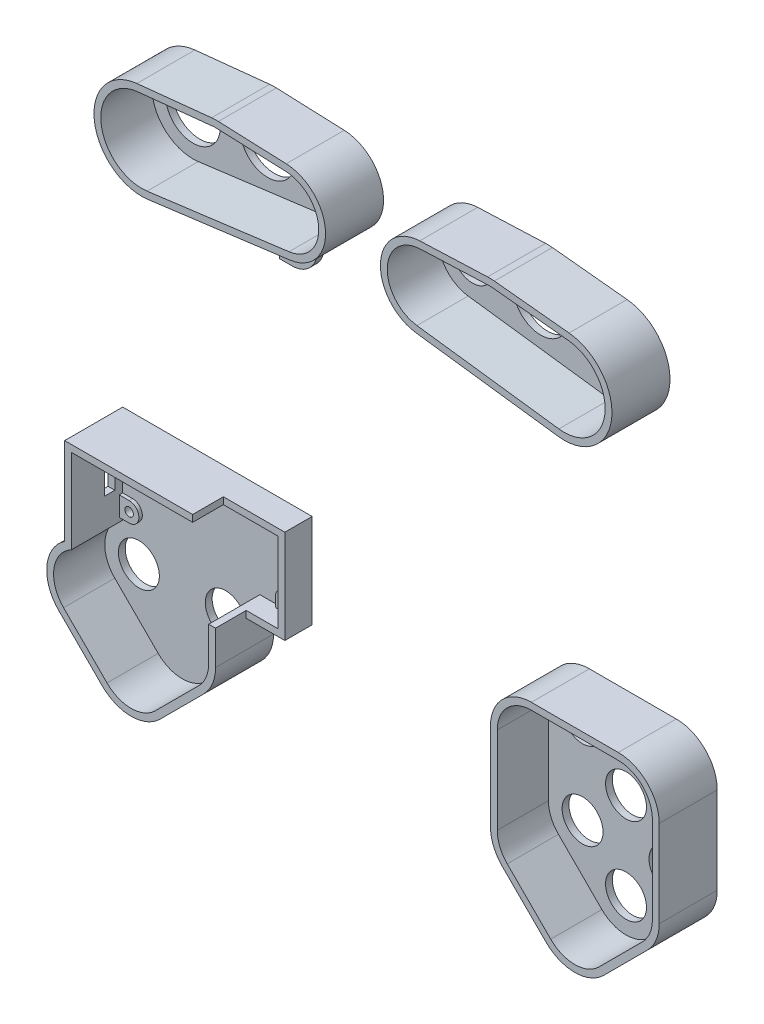
SolidWorks part; units mm, degrees
ref_plane "Front Plane" through (0, 0, 0) normal (0, 0, 1) x (1, 0, 0)
ref_plane "Top Plane" through (0, 0, 0) normal (0, 1, 0) x (1, 0, 0)
ref_plane "Right Plane" through (0, 0, 0) normal (1, 0, 0) x (0, 0, -1)
sketch "Sketch1" plane through (0, 0, 0) normal (0, 0, 1) x (1, 0, 0)
  line L10 (-86.2132, -68.4853) -> (-73.4853, -81.2132)
  line L11 (-56.5147, -81.2132) -> (-43.7868, -68.4853)
  line L12 (43.7868, -68.4853) -> (56.5147, -81.2132)
  line L13 (73.4853, -81.2132) -> (86.2132, -68.4853)
  line L14 (89.7279, -60) -> (89.7279, -34.5442)
  line L15 (63.3122, 76.6851) -> (41.4267, 78.9271)
  line L16 (39.439, 78.9888) -> (19.5552, 78.1913)
  line L17 (-19.5552, 78.1913) -> (-39.439, 78.9888)
  line L18 (-41.4267, 78.9271) -> (-63.3122, 76.6851)
  line L19 (-89.7279, -34.5442) -> (-89.7279, -60)
  line L20 (-86.2132, -68.4853) -> (-73.4853, -81.2132)
  line L21 (-56.5147, -81.2132) -> (-43.7868, -68.4853)
  line L22 (43.7868, -68.4853) -> (56.5147, -81.2132)
  line L23 (73.4853, -81.2132) -> (86.2132, -68.4853)
  line L24 (89.7279, -60) -> (89.7279, -34.5442)
  line L25 (63.3122, 76.6851) -> (41.4267, 78.9271)
  line L26 (39.439, 78.9888) -> (19.5552, 78.1913)
  line L27 (-19.5552, 78.1913) -> (-39.439, 78.9888)
  line L28 (-41.4267, 78.9271) -> (-63.3122, 76.6851)
  line L29 (-89.7279, -34.5442) -> (-89.7279, -60)
  line L30 (77.7279, -22.5442) -> (52.2721, -22.5442)
  line L31 (40.2721, -34.5442) -> (40.2721, -60)
  line L32 (-60.0743, 48.8756) -> (-18.4837, 54.3018)
  line L33 (60.0743, 48.8756) -> (18.4837, 54.3018)
  line L34 (-77.7279, -48) -> (-52.2721, -48)
  line L35 (-65, -48) -> (-65, -50) construction
  line L36 (-79.579, -29.36) -> (-33.859, -29.36)
  line L37 (-79.579, -29.36) -> (-79.579, -47.14)
  line L38 (-79.579, -47.14) -> (-33.859, -47.14)
  line L39 (-33.859, -29.36) -> (-33.859, -47.14)
  line L40 (-79.579, -29.36) -> (-33.859, -47.14) construction
  line L41 (-79.579, -47.14) -> (-33.859, -29.36) construction
  line L42 (-82.469, -26.5) -> (-30.969, -26.5)
  line L43 (-82.469, -26.5) -> (-82.469, -50)
  line L44 (-82.469, -50) -> (-30.969, -50)
  line L45 (-30.969, -26.5) -> (-30.969, -50)
  line L46 (-82.469, -26.5) -> (-30.969, -50) construction
  line L47 (-82.469, -50) -> (-30.969, -26.5) construction
  line L48 (-84.469, -52) -> (-28.969, -52)
  line L49 (-84.469, -52) -> (-84.469, -24.5)
  line L50 (-84.469, -24.5) -> (-28.969, -24.5)
  line L51 (-28.969, -52) -> (-28.969, -24.5)
  line L52 (-84.469, -52) -> (-28.969, -24.5) construction
  line L53 (-84.469, -24.5) -> (-28.969, -52) construction
  line L54 (-30.969, -26.5) -> (-28.969, -26.5) construction
  line L55 (-30.969, -26.5) -> (-30.969, -24.5) construction
  line L56 (-40.2721, -60) -> (-40.2721, -52)
  arc A16 (-89.7279, -60) -> (-86.2132, -68.4853) centre (-77.7279, -60) ccw
  arc A17 (-73.4853, -81.2132) -> (-56.5147, -81.2132) centre (-65, -72.7279) ccw
  arc A18 (43.7868, -68.4853) -> (-43.7868, -68.4853) centre (0, -112.2721) ccw
  arc A19 (56.5147, -81.2132) -> (73.4853, -81.2132) centre (65, -72.7279) ccw
  arc A20 (86.2132, -68.4853) -> (89.7279, -60) centre (77.7279, -60) ccw
  arc A21 (89.7279, -34.5442) -> (85.5204, -25.4185) centre (77.7279, -34.5442) ccw
  arc A22 (73.6585, 55.182) -> (85.5204, -25.4185) centre (125.7323, 21.6725) ccw
  arc A23 (73.6585, 55.182) -> (63.3122, 76.6851) centre (61.8855, 62.758) ccw
  arc A24 (41.4267, 78.9271) -> (39.439, 78.9888) centre (40, 65) ccw
  arc A25 (19.5552, 78.1913) -> (16.7836, 77.7518) centre (20.0361, 66.201) ccw
  arc A26 (-16.7836, 77.7518) -> (16.7836, 77.7518) centre (0, 137.3578) ccw
  arc A27 (-16.7836, 77.7518) -> (-19.5552, 78.1913) centre (-20.0361, 66.201) ccw
  arc A28 (-39.439, 78.9888) -> (-41.4267, 78.9271) centre (-40, 65) ccw
  arc A29 (-63.3122, 76.6851) -> (-73.6585, 55.182) centre (-61.8855, 62.758) ccw
  arc A30 (-85.5204, -25.4185) -> (-73.6585, 55.182) centre (-125.7323, 21.6725) ccw
  arc A31 (-85.5204, -25.4185) -> (-89.7279, -34.5442) centre (-77.7279, -34.5442) ccw
  arc A32 (-89.7279, -60) -> (-86.2132, -68.4853) centre (-77.7279, -60) ccw
  arc A33 (-73.4853, -81.2132) -> (-56.5147, -81.2132) centre (-65, -72.7279) ccw
  arc A34 (43.7868, -68.4853) -> (-43.7868, -68.4853) centre (0, -112.2721) ccw
  arc A35 (56.5147, -81.2132) -> (73.4853, -81.2132) centre (65, -72.7279) ccw
  arc A36 (86.2132, -68.4853) -> (89.7279, -60) centre (77.7279, -60) ccw
  arc A37 (89.7279, -34.5442) -> (85.5204, -25.4185) centre (77.7279, -34.5442) ccw
  arc A38 (73.6585, 55.182) -> (85.5204, -25.4185) centre (125.7323, 21.6725) ccw
  arc A39 (73.6585, 55.182) -> (63.3122, 76.6851) centre (61.8855, 62.758) ccw
  arc A40 (41.4267, 78.9271) -> (39.439, 78.9888) centre (40, 65) ccw
  arc A41 (19.5552, 78.1913) -> (16.7836, 77.7518) centre (20.0361, 66.201) ccw
  arc A42 (-16.7836, 77.7518) -> (16.7836, 77.7518) centre (0, 137.3578) ccw
  arc A43 (-16.7836, 77.7518) -> (-19.5552, 78.1913) centre (-20.0361, 66.201) ccw
  arc A44 (-39.439, 78.9888) -> (-41.4267, 78.9271) centre (-40, 65) ccw
  arc A45 (-63.3122, 76.6851) -> (-73.6585, 55.182) centre (-61.8855, 62.758) ccw
  arc A46 (-85.5204, -25.4185) -> (-73.6585, 55.182) centre (-125.7323, 21.6725) ccw
  arc A47 (-85.5204, -25.4185) -> (-89.7279, -34.5442) centre (-77.7279, -34.5442) ccw
  circle A48 centre (77.7279, -34.5442) radius 6 construction
  circle A49 centre (52.2721, -34.5442) radius 6 construction
  circle A50 centre (65, -47.2721) radius 6 construction
  circle A51 centre (77.7279, -60) radius 6 construction
  circle A52 centre (52.2721, -60) radius 6 construction
  circle A53 centre (65, -72.7279) radius 6 construction
  circle A54 centre (-52.2721, -60) radius 6 construction
  circle A55 centre (-77.7279, -60) radius 6 construction
  circle A56 centre (77.7279, -34.5442) radius 6
  circle A57 centre (52.2721, -34.5442) radius 6
  circle A58 centre (65, -47.2721) radius 6
  circle A59 centre (77.7279, -60) radius 6
  circle A60 centre (52.2721, -60) radius 6
  circle A61 centre (65, -72.7279) radius 6
  circle A62 centre (-52.2721, -60) radius 6
  circle A63 centre (-77.7279, -60) radius 6
  circle A64 centre (61.8855, 62.758) radius 8 construction
  circle A65 centre (40, 65) radius 8 construction
  circle A66 centre (20.0361, 66.201) radius 6 construction
  circle A67 centre (-20.0361, 66.201) radius 6 construction
  circle A68 centre (-40, 65) radius 8 construction
  circle A69 centre (-61.8855, 62.758) radius 8 construction
  circle A70 centre (61.8855, 62.758) radius 8
  circle A71 centre (40, 65) radius 8
  circle A72 centre (20.0361, 66.201) radius 6
  circle A73 centre (-20.0361, 66.201) radius 6
  circle A74 centre (-40, 65) radius 8
  circle A75 centre (-61.8855, 62.758) radius 8
  circle A76 centre (77.7279, -34.5442) radius 12
  circle A77 centre (52.2721, -34.5442) radius 12
  circle A78 centre (52.2721, -60) radius 12
  circle A79 centre (-61.8855, 62.758) radius 14
  circle A80 centre (-20.0361, 66.201) radius 12
  circle A81 centre (20.0361, 66.201) radius 12
  circle A82 centre (61.8855, 62.758) radius 14
  circle A83 centre (-77.7279, -60) radius 12
  circle A84 centre (-52.2721, -60) radius 12
  circle A85 centre (-79.579, -29.36) radius 1.25
  circle A86 centre (-33.859, -29.36) radius 1.25
  circle A87 centre (-33.859, -47.14) radius 1.25
  circle A88 centre (-79.579, -47.14) radius 1.25
  point P47 (-56.719, -38.25)
  point P66 (-56.719, -38.25)
  point P72 (-56.719, -38.25)
  dimension "D4" = 2.5
  dimension "D2" = 45.72
  dimension "D3" = 17.78
  dimension "D5" = 51.5
  dimension "D6" = 23.5
  dimension "D7" = 2
  dimension "D1" = 0
extrude "Boss-Extrude1" add sketch "Sketch1" along normal blind 2 contours A84 L34 A83 L20 A33 L21 | A83 A32 A63 | A84 A62 | A37 A76 A56 | A77 A58 A76 L30 | A77 A57 | A78 A58 A77 L31 | A78 L22 A35 L23 A36 L24 A76 A58 A61 A59 | A78 A60 | A79 A45 A75 | A80 A74 A79 L32 | A80 L27 A44 L28 A79 A74 | A43 A80 A73 | A41 A81 A72 | A82 L25 A40 L26 A81 A71 | A82 A71 A81 L33 | A39 A82 A70 | A84 L56 L48 | A84 L48 L51 L50 L49 A83 L43 L42 L45 L44 | L48 A84 L44 | A84 L44 A83 L48 | L48 A83 L44 L43 L49 | A88 A83 L43 L44 | A84 L34 A83 L44 | L44 A84 | A88 L37 A85 L36 A86 L39 A87 L38 A83 L34 A84 L44 L45 L42 L43 | A88 L38 A87 L39 A86 L36 A85 L37 region at (-65, -73.7209, 0) region at (-88.5141, -64.4678, 0) region at (-77.3432, -50.979, 0) region at (-83.8496, -37.2862, 0) region at (-65, -50.921, 0) region at (-60.3032, -68.4912, 0) region at (-77.3671, -49.1806, 0) region at (-81.9029, -37.7381, 0) region at (-52.2721, -51.0485, 0) region at (-65, -48.8938, 0) region at (52.2721, -72.6804, 0) region at (41.4991, -64.4623, 0) region at (-41.1646, -53.9455, 0) region at (-74.1443, 68.6564, 0) region at (-52.2721, -49.194, 0) region at (46.3766, -47.2721, 0) region at (-41.0869, 74.8949, 0) region at (-39.4755, 55.0305, 0) region at (-56.719, -38.25, 0) region at (44.0268, -26.2989, 0) region at (-27.4629, 57.2114, 0) region at (65, -28.6487, 0) region at (81.7633, -23.6041, 0) region at (18.2097, 77.7176, 0) region at (67.6138, 50.4188, 0) region at (41.0869, 74.8949, 0) region at (39.4755, 55.0305, 0)
sketch "Sketch2" plane through (0, 0, 2) normal (0, 0, 1) x (1, 0, 0)
  line L0 (40.2721, -34.5442) -> (40.2721, -60) construction
  line L1 (43.7868, -68.4853) -> (56.5147, -81.2132) construction
  line L2 (73.4853, -81.2132) -> (86.2132, -68.4853) construction
  line L3 (89.7279, -60) -> (89.7279, -34.5442) construction
  line L4 (77.7279, -22.5442) -> (52.2721, -22.5442) construction
  line L5 (18.4837, 54.3018) -> (60.0743, 48.8756) construction
  line L6 (63.3122, 76.6851) -> (41.4267, 78.9271) construction
  line L7 (39.439, 78.9888) -> (19.5552, 78.1913) construction
  line L8 (-19.5552, 78.1913) -> (-39.439, 78.9888) construction
  line L9 (-41.4267, 78.9271) -> (-63.3122, 76.6851) construction
  line L10 (-60.0743, 48.8756) -> (-18.4837, 54.3018) construction
  line L14 (40.2721, -34.5442) -> (40.2721, -60)
  line L15 (43.7868, -68.4853) -> (56.5147, -81.2132)
  line L16 (73.4853, -81.2132) -> (86.2132, -68.4853)
  line L17 (89.7279, -60) -> (89.7279, -34.5442)
  line L18 (77.7279, -22.5442) -> (52.2721, -22.5442)
  line L19 (18.4837, 54.3018) -> (60.0743, 48.8756)
  line L20 (63.3122, 76.6851) -> (41.4267, 78.9271)
  line L21 (39.439, 78.9888) -> (19.5552, 78.1913)
  line L22 (-19.5552, 78.1913) -> (-39.439, 78.9888)
  line L23 (-41.4267, 78.9271) -> (-63.3122, 76.6851)
  line L24 (-60.0743, 48.8756) -> (-18.4837, 54.3018)
  line L31 (-19.6354, 76.1929) -> (-39.5191, 76.9904)
  line L32 (-41.2229, 76.9375) -> (-63.1084, 74.6955)
  line L33 (-60.333, 50.8588) -> (-18.7424, 56.285)
  line L34 (18.7424, 56.285) -> (60.333, 50.8588)
  line L35 (63.1084, 74.6955) -> (41.2229, 76.9375)
  line L36 (39.5191, 76.9904) -> (19.6354, 76.1929)
  line L37 (42.2721, -34.5442) -> (42.2721, -60)
  line L38 (45.201, -67.0711) -> (57.9289, -79.799)
  line L39 (72.0711, -79.799) -> (84.799, -67.0711)
  line L40 (87.7279, -60) -> (87.7279, -34.5442)
  line L41 (77.7279, -24.5442) -> (52.2721, -24.5442)
  line L49 (-40.2721, -60) -> (-40.2721, -52)
  line L50 (-40.2721, -52) -> (-28.969, -52)
  line L51 (-28.969, -52) -> (-28.969, -24.5)
  line L52 (-28.969, -24.5) -> (-84.469, -24.5)
  line L53 (-84.469, -24.5) -> (-84.469, -50.0724)
  line L54 (-86.2132, -68.4853) -> (-73.4853, -81.2132)
  line L55 (-56.5147, -81.2132) -> (-43.7868, -68.4853)
  line L56 (-40.2721, -60) -> (-40.2721, -52)
  line L57 (-40.2721, -52) -> (-28.969, -52)
  line L58 (-28.969, -52) -> (-28.969, -24.5)
  line L59 (-28.969, -24.5) -> (-84.469, -24.5)
  line L60 (-84.469, -24.5) -> (-84.469, -50.0724)
  line L61 (-86.2132, -68.4853) -> (-73.4853, -81.2132)
  line L62 (-56.5147, -81.2132) -> (-43.7868, -68.4853)
  line L70 (-42.2721, -60) -> (-42.2721, -50)
  line L71 (-42.2721, -50) -> (-30.969, -50)
  line L72 (-30.969, -50) -> (-30.969, -26.5)
  line L73 (-30.969, -26.5) -> (-82.469, -26.5)
  line L74 (-82.469, -26.5) -> (-82.469, -51.1953)
  line L75 (-84.799, -67.0711) -> (-72.0711, -79.799)
  line L76 (-57.9289, -79.799) -> (-45.201, -67.0711)
  line L77 (-42.2721, -60) -> (-42.2721, -50)
  line L78 (-42.2721, -50) -> (-30.969, -50)
  line L79 (-30.969, -50) -> (-30.969, -26.5)
  line L80 (-30.969, -26.5) -> (-82.469, -26.5)
  line L81 (-82.469, -26.5) -> (-82.469, -51.1953)
  line L82 (-84.799, -67.0711) -> (-72.0711, -79.799)
  line L83 (-57.9289, -79.799) -> (-45.201, -67.0711)
  arc A0 (40.2721, -60) -> (43.7868, -68.4853) centre (52.2721, -60) ccw construction
  arc A1 (56.5147, -81.2132) -> (73.4853, -81.2132) centre (65, -72.7279) ccw construction
  arc A2 (86.2132, -68.4853) -> (89.7279, -60) centre (77.7279, -60) ccw construction
  arc A3 (89.7279, -34.5442) -> (77.7279, -22.5442) centre (77.7279, -34.5442) ccw construction
  arc A4 (52.2721, -22.5442) -> (40.2721, -34.5442) centre (52.2721, -34.5442) ccw construction
  arc A5 (60.0743, 48.8756) -> (63.3122, 76.6851) centre (61.8855, 62.758) ccw construction
  arc A6 (41.4267, 78.9271) -> (39.439, 78.9888) centre (40, 65) ccw construction
  arc A7 (19.5552, 78.1913) -> (18.4837, 54.3018) centre (20.0361, 66.201) ccw construction
  arc A8 (-18.4837, 54.3018) -> (-19.5552, 78.1913) centre (-20.0361, 66.201) ccw construction
  arc A9 (-39.439, 78.9888) -> (-41.4267, 78.9271) centre (-40, 65) ccw construction
  arc A10 (-63.3122, 76.6851) -> (-60.0743, 48.8756) centre (-61.8855, 62.758) ccw construction
  arc A14 (40.2721, -60) -> (43.7868, -68.4853) centre (52.2721, -60) ccw
  arc A15 (56.5147, -81.2132) -> (73.4853, -81.2132) centre (65, -72.7279) ccw
  arc A16 (86.2132, -68.4853) -> (89.7279, -60) centre (77.7279, -60) ccw
  arc A17 (89.7279, -34.5442) -> (77.7279, -22.5442) centre (77.7279, -34.5442) ccw
  arc A18 (52.2721, -22.5442) -> (40.2721, -34.5442) centre (52.2721, -34.5442) ccw
  arc A19 (60.0743, 48.8756) -> (63.3122, 76.6851) centre (61.8855, 62.758) ccw
  arc A20 (41.4267, 78.9271) -> (39.439, 78.9888) centre (40, 65) ccw
  arc A21 (19.5552, 78.1913) -> (18.4837, 54.3018) centre (20.0361, 66.201) ccw
  arc A22 (-18.4837, 54.3018) -> (-19.5552, 78.1913) centre (-20.0361, 66.201) ccw
  arc A23 (-39.439, 78.9888) -> (-41.4267, 78.9271) centre (-40, 65) ccw
  arc A24 (-63.3122, 76.6851) -> (-60.0743, 48.8756) centre (-61.8855, 62.758) ccw
  arc A31 (-18.7424, 56.285) -> (-19.6354, 76.1929) centre (-20.0361, 66.201) ccw
  arc A32 (-39.5191, 76.9904) -> (-41.2229, 76.9375) centre (-40, 65) ccw
  arc A33 (-63.1084, 74.6955) -> (-60.333, 50.8588) centre (-61.8855, 62.758) ccw
  arc A34 (60.333, 50.8588) -> (63.1084, 74.6955) centre (61.8855, 62.758) ccw
  arc A35 (41.2229, 76.9375) -> (39.5191, 76.9904) centre (40, 65) ccw
  arc A36 (19.6354, 76.1929) -> (18.7424, 56.285) centre (20.0361, 66.201) ccw
  arc A37 (42.2721, -60) -> (45.201, -67.0711) centre (52.2721, -60) ccw
  arc A38 (57.9289, -79.799) -> (72.0711, -79.799) centre (65, -72.7279) ccw
  arc A39 (84.799, -67.0711) -> (87.7279, -60) centre (77.7279, -60) ccw
  arc A40 (87.7279, -34.5442) -> (77.7279, -24.5442) centre (77.7279, -34.5442) ccw
  arc A41 (52.2721, -24.5442) -> (42.2721, -34.5442) centre (52.2721, -34.5442) ccw
  arc A45 (-84.469, -50.0724) -> (-86.2132, -68.4853) centre (-77.7279, -60) ccw
  arc A46 (-73.4853, -81.2132) -> (-56.5147, -81.2132) centre (-65, -72.7279) ccw
  arc A47 (-43.7868, -68.4853) -> (-40.2721, -60) centre (-52.2721, -60) ccw
  arc A48 (-84.469, -50.0724) -> (-86.2132, -68.4853) centre (-77.7279, -60) ccw
  arc A49 (-73.4853, -81.2132) -> (-56.5147, -81.2132) centre (-65, -72.7279) ccw
  arc A50 (-43.7868, -68.4853) -> (-40.2721, -60) centre (-52.2721, -60) ccw
  arc A54 (-82.469, -51.1953) -> (-84.799, -67.0711) centre (-77.7279, -60) ccw
  arc A55 (-72.0711, -79.799) -> (-57.9289, -79.799) centre (-65, -72.7279) ccw
  arc A56 (-45.201, -67.0711) -> (-42.2721, -60) centre (-52.2721, -60) ccw
  arc A57 (-82.469, -51.1953) -> (-84.799, -67.0711) centre (-77.7279, -60) ccw
  arc A58 (-72.0711, -79.799) -> (-57.9289, -79.799) centre (-65, -72.7279) ccw
  arc A59 (-45.201, -67.0711) -> (-42.2721, -60) centre (-52.2721, -60) ccw
  dimension "D1" = 2
  dimension "D2" = 0
  dimension "D3" = 2
extrude "Boss-Extrude2" add sketch "Sketch2" along normal blind 6
sketch "Sketch3" plane through (0, 0, 2) normal (0, 0, 1) x (1, 0, 0)
  line L0 (-30.969, -26.5) -> (-82.469, -26.5) construction
  line L1 (-76.719, -29.36) -> (-76.719, -26.5)
  line L2 (-79.579, -32.22) -> (-82.469, -32.22)
  line L3 (-82.469, -26.5) -> (-82.469, -51.1953) construction
  line L4 (-79.579, -44.28) -> (-82.469, -44.28)
  line L5 (-82.469, -26.5) -> (-82.469, -51.1953) construction
  line L6 (-79.579, -50) -> (-82.469, -50)
  line L7 (-36.719, -29.36) -> (-36.719, -26.5)
  line L8 (-30.969, -26.5) -> (-82.469, -26.5) construction
  line L9 (-33.859, -32.22) -> (-30.969, -32.22)
  line L10 (-30.969, -50) -> (-30.969, -26.5) construction
  line L11 (-33.859, -44.28) -> (-30.969, -44.28)
  line L12 (-36.719, -47.14) -> (-36.6205, -50)
  line L13 (-42.2721, -50) -> (-30.969, -50) construction
  line L21 (-57.9289, -79.799) -> (-45.201, -67.0711)
  line L22 (-42.2721, -60) -> (-42.2721, -50)
  line L23 (-42.2721, -50) -> (-30.969, -50)
  line L24 (-30.969, -50) -> (-30.969, -26.5)
  line L25 (-30.969, -26.5) -> (-82.469, -26.5)
  line L26 (-82.469, -26.5) -> (-82.469, -51.1953)
  line L27 (-84.799, -67.0711) -> (-72.0711, -79.799)
  line L28 (-57.9289, -79.799) -> (-45.201, -67.0711)
  line L29 (-42.2721, -60) -> (-42.2721, -50)
  line L30 (-42.2721, -50) -> (-30.969, -50)
  line L31 (-30.969, -50) -> (-30.969, -26.5)
  line L32 (-30.969, -26.5) -> (-82.469, -26.5)
  line L33 (-82.469, -26.5) -> (-82.469, -51.1953)
  line L34 (-84.799, -67.0711) -> (-72.0711, -79.799)
  circle A0 centre (-33.859, -47.14) radius 1.25 construction
  circle A1 centre (-33.859, -29.36) radius 1.25 construction
  circle A2 centre (-79.579, -47.14) radius 1.25 construction
  circle A3 centre (-79.579, -29.36) radius 1.25 construction
  circle A4 centre (-33.859, -47.14) radius 1.25
  circle A5 centre (-33.859, -29.36) radius 1.25
  circle A6 centre (-79.579, -47.14) radius 1.25
  circle A7 centre (-79.579, -29.36) radius 1.25
  circle A8 centre (-79.579, -29.36) radius 2.86
  circle A9 centre (-33.859, -29.36) radius 2.86
  circle A10 centre (-33.859, -47.14) radius 2.86
  circle A11 centre (-79.579, -47.14) radius 2.86
  arc A15 (-45.201, -67.0711) -> (-42.2721, -60) centre (-52.2721, -60) ccw
  arc A16 (-82.469, -51.1953) -> (-84.799, -67.0711) centre (-77.7279, -60) ccw
  arc A17 (-72.0711, -79.799) -> (-57.9289, -79.799) centre (-65, -72.7279) ccw
  arc A18 (-45.201, -67.0711) -> (-42.2721, -60) centre (-52.2721, -60) ccw
  arc A19 (-82.469, -51.1953) -> (-84.799, -67.0711) centre (-77.7279, -60) ccw
  arc A20 (-72.0711, -79.799) -> (-57.9289, -79.799) centre (-65, -72.7279) ccw
  circle M20 centre (-79.579, -29.36) radius 1.25
  circle M21 centre (-33.859, -47.14) radius 1.25
  circle M22 centre (-33.859, -29.36) radius 1.25
  circle M23 centre (-79.579, -47.14) radius 1.25
  line M27 (-42.2721, -50) -> (-30.969, -50)
  line M28 (-30.969, -50) -> (-30.969, -26.5)
  line M29 (-30.969, -26.5) -> (-82.469, -26.5)
  line M30 (-82.469, -26.5) -> (-82.469, -51.1953)
  dimension "D1" = 0
extrude "Boss-Extrude3" add sketch "Sketch3" along normal blind 1 contours A8 M20 | A8 L1 M29 | A8 L32 L2 M30 | A9 L32 L7 | A9 M22 | A9 L9 M28 M29 | A10 L30 L11 M28 | A10 L12 M21 | A10 L12 M27 | A11 L4 L6 M30 | A11 M23 region at (-77.3578, -27.1388, 2) region at (-77.6139, -31.3251, 2) region at (-81.024, -32.1559, 2) region at (-36.0802, -27.1388, 2) region at (-35.8241, -27.3949, 2) region at (-32.414, -26.5641, 2) region at (-81.024, -44.3441, 2) region at (-77.6139, -45.1749, 2) region at (-30.9754, -47.14, 2) region at (-31.8939, -45.1749, 2) region at (-36.0274, -49.3883, 2)
sketch "Sketch4" plane through (0, 0, 8) normal (0, 0, 1) x (1, 0, 0)
  line L0 (-40.2721, -52) -> (-40.2721, -50)
  line L1 (-46.969, -26.5) -> (-46.969, -24.5)
  line L4 (-19.5552, 78.1913) -> (-39.439, 78.9888)
  line L5 (-41.4267, 78.9271) -> (-63.3122, 76.6851)
  line L6 (-60.0743, 48.8756) -> (-18.4837, 54.3018)
  line L7 (-40.2721, -60) -> (-40.2721, -52)
  line L8 (-40.2721, -52) -> (-28.969, -52)
  line L9 (-28.969, -52) -> (-28.969, -24.5)
  line L10 (-28.969, -24.5) -> (-84.469, -24.5)
  line L11 (-84.469, -24.5) -> (-84.469, -50.0724)
  line L12 (-86.2132, -68.4853) -> (-73.4853, -81.2132)
  line L13 (-56.5147, -81.2132) -> (-43.7868, -68.4853)
  line L14 (-40.2721, -60) -> (-40.2721, -52)
  line L15 (-40.2721, -52) -> (-28.969, -52)
  line L16 (-28.969, -52) -> (-28.969, -24.5)
  line L17 (-28.969, -24.5) -> (-84.469, -24.5)
  line L18 (-84.469, -24.5) -> (-84.469, -50.0724)
  line L19 (-86.2132, -68.4853) -> (-73.4853, -81.2132)
  line L20 (-56.5147, -81.2132) -> (-43.7868, -68.4853)
  line L21 (-19.5552, 78.1913) -> (-39.439, 78.9888)
  line L22 (-42.2721, -60) -> (-42.2721, -50)
  line L23 (-57.9289, -79.799) -> (-45.201, -67.0711)
  line L24 (-84.799, -67.0711) -> (-72.0711, -79.799)
  line L25 (-82.469, -26.5) -> (-82.469, -51.1953)
  line L26 (-30.969, -26.5) -> (-82.469, -26.5)
  line L27 (-30.969, -50) -> (-30.969, -26.5)
  line L28 (-42.2721, -50) -> (-30.969, -50)
  line L29 (-42.2721, -60) -> (-42.2721, -50)
  line L30 (-57.9289, -79.799) -> (-45.201, -67.0711)
  line L31 (-84.799, -67.0711) -> (-72.0711, -79.799)
  line L32 (-82.469, -26.5) -> (-82.469, -51.1953)
  line L33 (-30.969, -26.5) -> (-82.469, -26.5)
  line L34 (-30.969, -50) -> (-30.969, -26.5)
  line L35 (-42.2721, -50) -> (-30.969, -50)
  line L36 (-41.4267, 78.9271) -> (-63.3122, 76.6851)
  line L37 (-60.0743, 48.8756) -> (-18.4837, 54.3018)
  line L38 (-19.6354, 76.1929) -> (-39.5191, 76.9904)
  line L39 (-60.333, 50.8588) -> (-18.7424, 56.285)
  line L40 (-41.2229, 76.9375) -> (-63.1084, 74.6955)
  line L41 (-19.6354, 76.1929) -> (-39.5191, 76.9904)
  line L42 (-60.333, 50.8588) -> (-18.7424, 56.285)
  line L43 (-41.2229, 76.9375) -> (-63.1084, 74.6955)
  line L44 (18.4837, 54.3018) -> (60.0743, 48.8756)
  line L45 (63.3122, 76.6851) -> (41.4267, 78.9271)
  line L46 (39.439, 78.9888) -> (19.5552, 78.1913)
  line L47 (18.4837, 54.3018) -> (60.0743, 48.8756)
  line L48 (63.3122, 76.6851) -> (41.4267, 78.9271)
  line L49 (39.439, 78.9888) -> (19.5552, 78.1913)
  line L50 (18.7424, 56.285) -> (60.333, 50.8588)
  line L51 (39.5191, 76.9904) -> (19.6354, 76.1929)
  line L52 (63.1084, 74.6955) -> (41.2229, 76.9375)
  line L53 (18.7424, 56.285) -> (60.333, 50.8588)
  line L54 (39.5191, 76.9904) -> (19.6354, 76.1929)
  line L55 (63.1084, 74.6955) -> (41.2229, 76.9375)
  line L58 (40.2721, -34.5442) -> (40.2721, -60)
  line L59 (43.7868, -68.4853) -> (56.5147, -81.2132)
  line L60 (73.4853, -81.2132) -> (86.2132, -68.4853)
  line L61 (89.7279, -60) -> (89.7279, -34.5442)
  line L62 (77.7279, -22.5442) -> (52.2721, -22.5442)
  line L63 (40.2721, -34.5442) -> (40.2721, -60)
  line L64 (43.7868, -68.4853) -> (56.5147, -81.2132)
  line L65 (73.4853, -81.2132) -> (86.2132, -68.4853)
  line L66 (89.7279, -60) -> (89.7279, -34.5442)
  line L67 (77.7279, -22.5442) -> (52.2721, -22.5442)
  line L69 (42.2721, -34.5442) -> (42.2721, -60)
  line L70 (77.7279, -24.5442) -> (52.2721, -24.5442)
  line L71 (87.7279, -60) -> (87.7279, -34.5442)
  line L72 (72.0711, -79.799) -> (84.799, -67.0711)
  line L73 (45.201, -67.0711) -> (57.9289, -79.799)
  line L74 (42.2721, -34.5442) -> (42.2721, -60)
  line L75 (77.7279, -24.5442) -> (52.2721, -24.5442)
  line L76 (87.7279, -60) -> (87.7279, -34.5442)
  line L77 (72.0711, -79.799) -> (84.799, -67.0711)
  line L78 (45.201, -67.0711) -> (57.9289, -79.799)
  arc A3 (-43.7868, -68.4853) -> (-40.2721, -60) centre (-52.2721, -60) ccw
  arc A4 (-84.469, -50.0724) -> (-86.2132, -68.4853) centre (-77.7279, -60) ccw
  arc A5 (-73.4853, -81.2132) -> (-56.5147, -81.2132) centre (-65, -72.7279) ccw
  arc A6 (-43.7868, -68.4853) -> (-40.2721, -60) centre (-52.2721, -60) ccw
  arc A7 (-84.469, -50.0724) -> (-86.2132, -68.4853) centre (-77.7279, -60) ccw
  arc A8 (-73.4853, -81.2132) -> (-56.5147, -81.2132) centre (-65, -72.7279) ccw
  arc A9 (-45.201, -67.0711) -> (-42.2721, -60) centre (-52.2721, -60) ccw
  arc A10 (-72.0711, -79.799) -> (-57.9289, -79.799) centre (-65, -72.7279) ccw
  arc A11 (-82.469, -51.1953) -> (-84.799, -67.0711) centre (-77.7279, -60) ccw
  arc A12 (-45.201, -67.0711) -> (-42.2721, -60) centre (-52.2721, -60) ccw
  arc A13 (-72.0711, -79.799) -> (-57.9289, -79.799) centre (-65, -72.7279) ccw
  arc A14 (-82.469, -51.1953) -> (-84.799, -67.0711) centre (-77.7279, -60) ccw
  arc A15 (-18.4837, 54.3018) -> (-19.5552, 78.1913) centre (-20.0361, 66.201) ccw
  arc A16 (-39.439, 78.9888) -> (-41.4267, 78.9271) centre (-40, 65) ccw
  arc A17 (-63.3122, 76.6851) -> (-60.0743, 48.8756) centre (-61.8855, 62.758) ccw
  arc A18 (-18.4837, 54.3018) -> (-19.5552, 78.1913) centre (-20.0361, 66.201) ccw
  arc A19 (-39.439, 78.9888) -> (-41.4267, 78.9271) centre (-40, 65) ccw
  arc A20 (-63.3122, 76.6851) -> (-60.0743, 48.8756) centre (-61.8855, 62.758) ccw
  arc A22 (-18.7424, 56.285) -> (-19.6354, 76.1929) centre (-20.0361, 66.201) ccw
  arc A23 (-63.1084, 74.6955) -> (-60.333, 50.8588) centre (-61.8855, 62.758) ccw
  arc A24 (-39.5191, 76.9904) -> (-41.2229, 76.9375) centre (-40, 65) ccw
  arc A25 (-18.7424, 56.285) -> (-19.6354, 76.1929) centre (-20.0361, 66.201) ccw
  arc A26 (-63.1084, 74.6955) -> (-60.333, 50.8588) centre (-61.8855, 62.758) ccw
  arc A27 (-39.5191, 76.9904) -> (-41.2229, 76.9375) centre (-40, 65) ccw
  arc A28 (19.5552, 78.1913) -> (18.4837, 54.3018) centre (20.0361, 66.201) ccw
  arc A29 (60.0743, 48.8756) -> (63.3122, 76.6851) centre (61.8855, 62.758) ccw
  arc A30 (41.4267, 78.9271) -> (39.439, 78.9888) centre (40, 65) ccw
  arc A31 (19.5552, 78.1913) -> (18.4837, 54.3018) centre (20.0361, 66.201) ccw
  arc A32 (60.0743, 48.8756) -> (63.3122, 76.6851) centre (61.8855, 62.758) ccw
  arc A33 (41.4267, 78.9271) -> (39.439, 78.9888) centre (40, 65) ccw
  arc A35 (19.6354, 76.1929) -> (18.7424, 56.285) centre (20.0361, 66.201) ccw
  arc A36 (41.2229, 76.9375) -> (39.5191, 76.9904) centre (40, 65) ccw
  arc A37 (60.333, 50.8588) -> (63.1084, 74.6955) centre (61.8855, 62.758) ccw
  arc A38 (19.6354, 76.1929) -> (18.7424, 56.285) centre (20.0361, 66.201) ccw
  arc A39 (41.2229, 76.9375) -> (39.5191, 76.9904) centre (40, 65) ccw
  arc A40 (60.333, 50.8588) -> (63.1084, 74.6955) centre (61.8855, 62.758) ccw
  arc A43 (52.2721, -22.5442) -> (40.2721, -34.5442) centre (52.2721, -34.5442) ccw
  arc A44 (40.2721, -60) -> (43.7868, -68.4853) centre (52.2721, -60) ccw
  arc A45 (56.5147, -81.2132) -> (73.4853, -81.2132) centre (65, -72.7279) ccw
  arc A46 (86.2132, -68.4853) -> (89.7279, -60) centre (77.7279, -60) ccw
  arc A47 (89.7279, -34.5442) -> (77.7279, -22.5442) centre (77.7279, -34.5442) ccw
  arc A48 (52.2721, -22.5442) -> (40.2721, -34.5442) centre (52.2721, -34.5442) ccw
  arc A49 (40.2721, -60) -> (43.7868, -68.4853) centre (52.2721, -60) ccw
  arc A50 (56.5147, -81.2132) -> (73.4853, -81.2132) centre (65, -72.7279) ccw
  arc A51 (86.2132, -68.4853) -> (89.7279, -60) centre (77.7279, -60) ccw
  arc A52 (89.7279, -34.5442) -> (77.7279, -22.5442) centre (77.7279, -34.5442) ccw
  arc A53 (52.2721, -24.5442) -> (42.2721, -34.5442) centre (52.2721, -34.5442) ccw
  arc A54 (87.7279, -34.5442) -> (77.7279, -24.5442) centre (77.7279, -34.5442) ccw
  arc A55 (84.799, -67.0711) -> (87.7279, -60) centre (77.7279, -60) ccw
  arc A56 (57.9289, -79.799) -> (72.0711, -79.799) centre (65, -72.7279) ccw
  arc A57 (42.2721, -60) -> (45.201, -67.0711) centre (52.2721, -60) ccw
  arc A58 (52.2721, -24.5442) -> (42.2721, -34.5442) centre (52.2721, -34.5442) ccw
  arc A59 (87.7279, -34.5442) -> (77.7279, -24.5442) centre (77.7279, -34.5442) ccw
  arc A60 (84.799, -67.0711) -> (87.7279, -60) centre (77.7279, -60) ccw
  arc A61 (57.9289, -79.799) -> (72.0711, -79.799) centre (65, -72.7279) ccw
  arc A62 (42.2721, -60) -> (45.201, -67.0711) centre (52.2721, -60) ccw
  arc M65 (-43.7868, -68.4853) -> (-40.2721, -60) centre (-52.2721, -60) ccw
  line M66 (-40.2721, -60) -> (-40.2721, -52)
  arc M71 (-84.469, -50.0724) -> (-86.2132, -68.4853) centre (-77.7279, -60) ccw
  line M72 (-86.2132, -68.4853) -> (-73.4853, -81.2132)
  arc M73 (-73.4853, -81.2132) -> (-56.5147, -81.2132) centre (-65, -72.7279) ccw
  line M74 (-56.5147, -81.2132) -> (-43.7868, -68.4853)
  line M75 (-42.2721, -50) -> (-42.2721, -60)
  arc M76 (-42.2721, -60) -> (-45.201, -67.0711) centre (-52.2721, -60) cw
  line M77 (-45.201, -67.0711) -> (-57.9289, -79.799)
  arc M78 (-57.9289, -79.799) -> (-72.0711, -79.799) centre (-65, -72.7279) cw
  line M79 (-72.0711, -79.799) -> (-84.799, -67.0711)
  arc M80 (-84.799, -67.0711) -> (-82.469, -51.1953) centre (-77.7279, -60) cw
  dimension "D9" = 18
  dimension "D1" = 0
  dimension "D2" = 0
  dimension "D3" = 0
  dimension "D4" = 0
  dimension "D5" = 0
  dimension "D6" = 0
  dimension "D7" = 0
  dimension "D8" = 0
extrude "Boss-Extrude4" add sketch "Sketch4" along normal offset from surface (9 mm away) 15 contours M66 M75 M76 M77 M78 M79 M80 M71 M72 M73 M74 M65 | L66 A52 L67 A48 L63 A49 L64 A50 L65 A51 A62 L74 A58 L75 A59 L76 A60 L77 A61 L78 | L48 A33 L49 A31 L47 A32 A40 L53 A38 L54 A39 L55 | L36 A20 L37 A18 L21 A19 A27 L41 A25 L42 A26 L43 region at (-41.0514, -56, 8) region at (-8.7902, 66.7054, 8) region at (8.7902, 66.7054, 8) region at (44.3486, -26.6207, 8) up to face at (-40.9173, 68.4989, 2) offset beyond the face yes
sketch "Sketch5" plane through (-84.469, 0, 0) normal (-1, 0, 0) x (0, 0, 1)
  line L0 (5.8, -24.5) -> (5.8, -50.0724) construction
  line L1 (17, -24.5) -> (0, -24.5) construction
  line L2 (17, -50.0724) -> (0, -50.0724) construction
  line L4 (3, -26.5) -> (3, -32.22) construction
  line L5 (17, -26.5) -> (3, -26.5) construction
  line L6 (7.3, -42.45) -> (4.3, -42.45)
  line L7 (7.3, -42.45) -> (7.3, -34.45)
  line L8 (7.3, -34.45) -> (4.3, -34.45)
  line L9 (4.3, -42.45) -> (4.3, -34.45)
  line L10 (7.3, -42.45) -> (4.3, -34.45) construction
  line L11 (7.3, -34.45) -> (4.3, -42.45) construction
  line L12 (17, -26.5) -> (3, -26.5)
  line L13 (3, -26.5) -> (3, -32.22)
  point P6 (7.5044, -39.75)
  point P8 (5.8, -38.45)
  dimension "D1" = 1.3
  dimension "D2" = 8
  dimension "D3" = 3
  dimension "D4" = 11.95
extrude "Cut-Extrude1" cut sketch "Sketch5" against normal up to next contours L9 L6 L7 L8 region at (-84.469, -38.45, 5.8)
sketch "Sketch6" plane through (0, 0, 0) normal (0, 0, -1) x (-1, 0, 0)
  line L0 (0, 20.9977) -> (0, -14.9066) construction
  line L1 (15.8114, 22.5) -> (-15.8114, 22.5)
  line L2 (27.5, 22.5) -> (-27.5, 22.5)
  line L3 (27.5, 22.5) -> (27.5, 52.5)
  line L4 (27.5, 52.5) -> (-27.5, 52.5)
  line L5 (-27.5, 22.5) -> (-27.5, 52.5)
  line L6 (27.5, 22.5) -> (-27.5, 52.5) construction
  line L7 (27.5, 52.5) -> (-27.5, 22.5) construction
  line L8 (27.5, 53.1255) -> (27.5, 45.1255)
  line L9 (60.0743, 48.8756) -> (18.4837, 54.3018) construction
  line L10 (27.5, 45.1255) -> (29.5, 45.1255)
  line L11 (29.5, 45.1255) -> (29.5, 52.8645)
  line L12 (29.5, 52.8645) -> (27.5, 53.1255)
  line L13 (27.5, 53.1255) -> (18.4837, 54.3018)
  line L14 (18.4837, 54.3018) -> (18.4837, 52.5)
  line L16 (27.5, 53.1255) -> (18.4837, 54.3018)
  line L17 (-27.5, 45.1255) -> (-29.5, 45.1255)
  line L18 (-29.5, 45.1255) -> (-29.5, 52.8645)
  line L19 (-29.5, 52.8645) -> (-27.5, 53.1255)
  line L20 (-18.4837, 54.3018) -> (-18.4837, 52.5)
  line L21 (-27.5, 53.1255) -> (-18.4837, 54.3018)
  circle A0 centre (0, 0) radius 27.5
  point P1 (0, 37.5)
  point P12 (0, 27.5)
  line M8 (18.4837, 54.3018) -> (60.0743, 48.8756)
  dimension "D3" = 55
  dimension "D1" = 30
  dimension "D2" = 55
  dimension "D4" = 5
  dimension "D6" = 2
  dimension "D7" = 8
extrude "Boss-Extrude5" add sketch "Sketch6" against normal blind 7 contours L10 L11 L8 L3 M8 | L14 L4 L8 M8 | L21 L19 L18 L17 L5 L4 L20 region at (-28.4945, 49.0606, 0) region at (28.5, 45.2689, 0) region at (-22.2636, 53.1543, 0)
sketch "Sketch7" plane through (0, 0, 7) normal (0, 0, 1) x (1, 0, 0)
  line L0 (-18.4837, 54.3018) -> (-18.4837, 52.5)
  line L1 (-25.8582, 45.1255) -> (-27.5, 45.1255)
  line L2 (-27.5, 45.1255) -> (-29.5, 45.1255) construction
  line L3 (0, 21.2673) -> (0, -12.7105) construction
  line L4 (29.5, 52.8645) -> (29.5, 45.1255)
  line L5 (29.5, 45.1255) -> (27.5, 45.1255)
  line L6 (25.8582, 45.1255) -> (27.5, 45.1255)
  line L7 (18.4837, 54.3018) -> (18.4837, 52.5)
  line L8 (18.4837, 54.3018) -> (29.5, 52.8645)
  line L9 (-29.5, 45.1255) -> (-27.5, 45.1255)
  line L10 (-27.5, 45.1255) -> (-27.5, 52.5)
  line L11 (-27.5, 52.5) -> (-18.4837, 52.5)
  line L12 (-18.4837, 52.5) -> (-18.4837, 54.3018)
  line L13 (-18.4837, 54.3018) -> (-29.5, 52.8645)
  line L14 (-29.5, 52.8645) -> (-29.5, 45.1255)
  line L15 (-29.5, 45.1255) -> (-27.5, 45.1255)
  line L16 (-27.5, 45.1255) -> (-27.5, 52.5)
  line L17 (-27.5, 52.5) -> (-18.4837, 52.5)
  line L18 (-18.4837, 52.5) -> (-18.4837, 54.3018)
  line L19 (-18.4837, 54.3018) -> (-29.5, 52.8645)
  line L20 (-29.5, 52.8645) -> (-29.5, 45.1255)
  arc A0 (-18.4837, 52.5) -> (-25.8582, 45.1255) centre (-25.8582, 52.5) cw
  arc A1 (18.4837, 52.5) -> (25.8582, 45.1255) centre (25.8582, 52.5) ccw
  line M10 (-29.5, 45.1255) -> (-27.5, 45.1255)
  line M11 (-27.5, 45.1255) -> (-27.5, 52.5)
  line M12 (-27.5, 52.5) -> (-18.4837, 52.5)
  line M13 (-18.4837, 52.5) -> (-18.4837, 54.3018)
  line M14 (-18.4837, 54.3018) -> (-29.5, 52.8645)
  line M15 (-29.5, 52.8645) -> (-29.5, 45.1255)
  dimension "D1" = 0
extrude "Boss-Extrude6" add sketch "Sketch7" along normal blind 2 contours M15 M10 M11 M12 M13 M14 | A0 L1 M12 M11 | L7 A1 L6 L5 L4 L8 region at (-18.627, 53.4009, 7) region at (-23.6009, 49.247, 7) region at (24.3664, 49.7356, 7)
